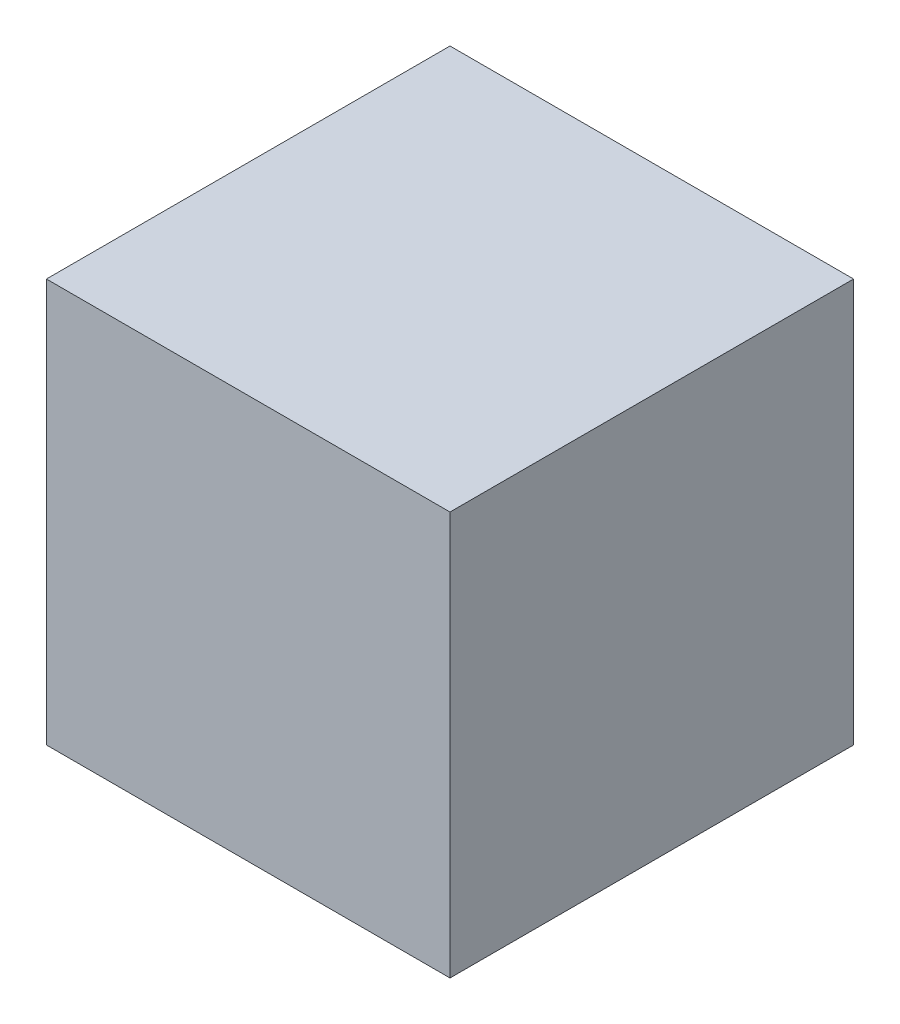
SolidWorks part; units mm, degrees
ref_plane "Front Plane" through (0, 0, 0) normal (0, 0, 1) x (1, 0, 0)
ref_plane "Top Plane" through (0, 0, 0) normal (0, 1, 0) x (1, 0, 0)
ref_plane "Right Plane" through (0, 0, 0) normal (1, 0, 0) x (0, 0, -1)
sketch "Sketch1" plane through (0, 0, 0) normal (0, 1, 0) x (1, 0, 0)
  line L1 (-33.25, -33.25) -> (33.25, -33.25)
  line L2 (-33.25, -33.25) -> (-33.25, 33.25)
  line L3 (-33.25, 33.25) -> (33.25, 33.25)
  line L4 (33.25, -33.25) -> (33.25, 33.25)
  line L5 (-33.25, -33.25) -> (33.25, 33.25) construction
  line L6 (-33.25, 33.25) -> (33.25, -33.25) construction
  point P0 (0, 0)
  dimension "D1" = 66.5
  dimension "D2" = 66.5
extrude "Boss-Extrude1" add sketch "Sketch1" along normal blind 33.25 and the other way blind 33.25
sketch "Sketch2" plane through (0, 0, 0) normal (0, 1, 0) x (1, 0, 0)
  line L0 (-11.0833, 0) -> (11.0833, 0)
  arc A0 (11.0833, 0) -> (-11.0833, 0) centre (0, 0) ccw
  point P6 (0, 0)
  dimension "D1" = 11.0833
revolve "Cut-Revolve1" cut sketch "Sketch2" angle 360 about L0
sketch "Sketch3" plane through (0, 0, 0) normal (0, 0, 1) x (1, 0, 0)
  line L0 (-32, 0) -> (32, 0) construction
  line L1 (-31.5315, -12.4842) -> (31.5315, 12.4842) construction
  line L2 (33.25, 22.1667) -> (29.25, 22.1667)
  line L3 (-31.5217, -22.9019) -> (31.5217, 22.9019) construction
  line L4 (-32.2525, -4.0744) -> (32.2525, 4.0744) construction
  line L5 (33.25, 13.3) -> (29.25, 13.3)
  line L6 (33.25, 22.1667) -> (47.0226, 22.1667)
  line L7 (33.25, -33.25) -> (33.25, 33.25) construction
  line L8 (33.25, 13.3) -> (47.0226, 13.3)
  line L9 (-32, -32) -> (32, 32) construction
  line L10 (33.25, 4.4333) -> (29.25, 4.4333)
  line L11 (33.25, 4.4333) -> (47.0226, 4.4333)
  line L12 (33.25, 22.1667) -> (33.25, 13.3) construction
  line L13 (29.5514, 1.3891) -> (10.9959, 1.3891)
  line L14 (29.6913, 21.572) -> (13.9557, 10.1394)
  line L15 (29.8754, 11.8285) -> (21.7727, 8.6204)
  line L16 (-32, -1.3891) -> (32, -1.3891) construction
  line L17 (-32, 1.3891) -> (32, 1.3891) construction
  line L18 (33.25, -22.1667) -> (47.0226, -22.1667)
  line L19 (33.25, -22.1667) -> (29.25, -22.1667)
  line L20 (33.25, -13.3) -> (47.0226, -13.3)
  line L21 (33.25, -13.3) -> (29.25, -13.3)
  line L22 (29.6913, -21.572) -> (13.9557, -10.1394)
  line L23 (29.8754, -11.8285) -> (21.7727, -8.6204)
  line L24 (33.25, -4.4333) -> (47.0226, -4.4333)
  line L25 (33.25, -4.4333) -> (29.25, -4.4333)
  line L26 (29.5514, -1.3891) -> (10.9959, -1.3891)
  line L27 (0, -33.25) -> (0, 33.25) construction
  circle A0 centre (0, 0) radius 11.0833 construction
  arc A1 (29.25, 22.1667) -> (29.6913, 21.572) centre (0, 0) cw
  arc A2 (29.25, 13.3) -> (29.8754, 11.8285) centre (0, 0) cw
  arc A3 (29.25, 4.4333) -> (29.5514, 1.3891) centre (0, 0) cw
  circle A6 centre (0, 0) radius 17.2502 construction
  circle A7 centre (0, 0) radius 23.4172 construction
  arc A8 (10.9959, 1.3891) -> (10.9959, -1.3891) centre (0, 0) cw
  arc A9 (21.7727, 8.6204) -> (23.3759, 1.3891) centre (0, 0) cw
  arc A10 (13.9557, 10.1394) -> (17.1942, 1.3891) centre (0, 0) cw
  arc A11 (10.9959, 1.3891) -> (7.8371, 7.8371) centre (0, 0) ccw
  arc A12 (29.25, -22.1667) -> (29.6913, -21.572) centre (0, 0) ccw
  arc A13 (29.25, -13.3) -> (29.8754, -11.8285) centre (0, 0) ccw
  arc A14 (29.25, -4.4333) -> (29.5514, -1.3891) centre (0, 0) ccw
  arc A15 (21.7727, -8.6204) -> (23.3759, -1.3891) centre (0, 0) ccw
  arc A16 (13.9557, -10.1394) -> (17.1942, -1.3891) centre (0, 0) ccw
  arc A17 (10.9959, -1.3891) -> (7.8371, -7.8371) centre (0, 0) cw
  point P4 (0, 0)
  point P5 (0, 0)
  point P7 (0, 0)
  point P9 (0, 0)
  point P10 (0, 0)
  point P11 (0, 0)
  point P13 (0, 0)
  point P14 (0, 0)
  point P15 (0, 0)
  point P17 (0, 0)
  point P18 (0, 0)
  point P21 (0, 0)
  point P22 (0, 0)
  point P23 (0, 0)
  point P24 (0, 0)
  point P27 (0, 0)
  point P28 (0, 0)
  point P38 (0, 0)
  point P40 (0, 0)
  point P55 (29.3508, 3.7079)
  point P68 (0, 0)
  point P88 (0, 0)
  dimension "D8" = 22.1667
  dimension "D1" = 7.2
  dimension "D2" = 14.4
  dimension "D3" = 14.4
  dimension "D4" = 11.0833
  dimension "D5" = 13.7726
  dimension "D7" = 9
  dimension "D6" = 4
  dimension "D9" = 8.8667
  dimension "D13" = 18.5007
  dimension "D10" = 1.3891
  dimension "D11" = 1.3891
  dimension "D14" = 6.1669
  dimension "D15" = 6.1669
  dimension "D12" = 3
equation "\"edge_length\"= 66.5mm"
equation "\"D1@Sketch1\" = \"edge_length\""
equation "\"D2@Sketch1\" = \"edge_length\""
equation "\"D1@Boss-Extrude1\"=\"edge_length\"/2"
equation "\"D2@Boss-Extrude1\"=\"edge_length\"/2"
equation "\"core_diameter\"= \"edge_length\" / 3"
equation "\"latch_depth\"= \"edge_length\" / 27"
equation "\"D1@Sketch2\"=\"core_diameter\"/2"
equation "\"cap_depth\" = 1.5mm"
equation "\"D4@Sketch3\" = \"edge_length\" / 6"
equation "\"D5@Sketch3\" = \"edge_length\" *  ( sqr ( 2 )  - 1 )  / 2"
equation "\"D8@Sketch3\" = \"core_diameter\""
equation "\"D9@Sketch3\" = \"edge_length\" * 2 / 15"
equation "\"extra_cap_depth\"= 2.5mm"
equation "\"screw_diameter\"= \"core_diameter\" * sin ( 7.2 )"
equation "\"D11@Sketch3\" = \"screw_diameter\" / 2"
equation "\"D10@Sketch3\" = \"screw_diameter\" / 2"
equation "\"D15@Sketch3\" = \"D13@Sketch3\" / 3"
equation "\"D14@Sketch3\" = \"D13@Sketch3\" / 3"
equation "\"D6@Sketch3\" = \"cap_depth\" + \"extra_cap_depth\""
